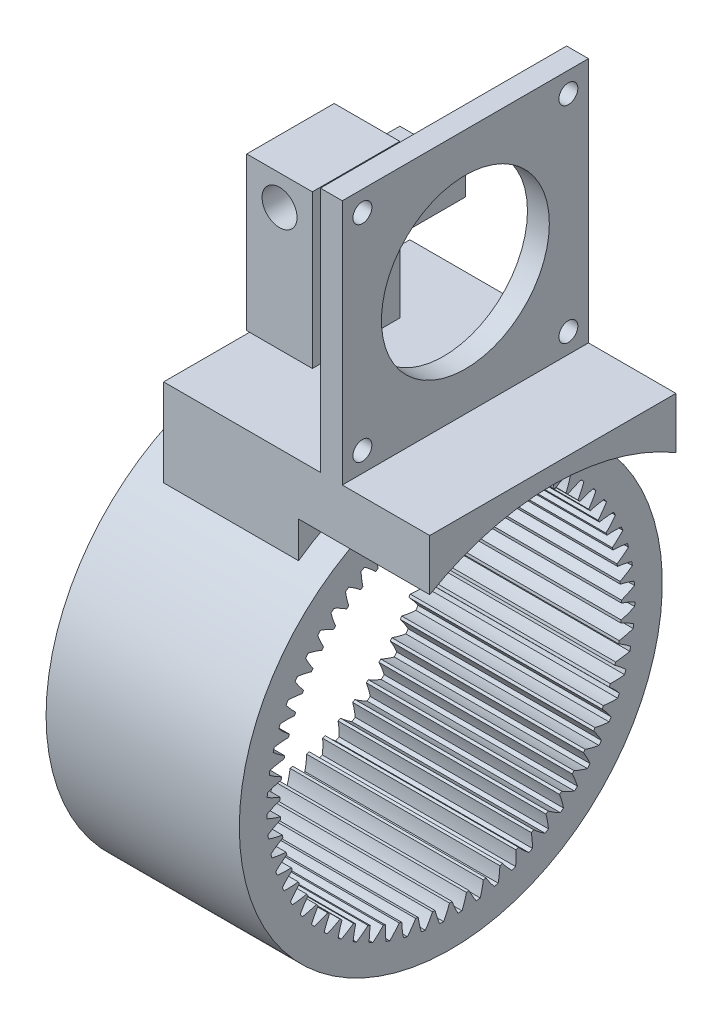
SolidWorks part; units mm, degrees
ref_plane "Plane1" through (0, 0, 0) normal (0, 0, 1) x (1, 0, 0)
ref_plane "Plane2" through (0, 0, 0) normal (0, 1, 0) x (1, 0, 0)
ref_plane "Plane3" through (0, 0, 0) normal (1, 0, 0) x (0, 0, -1)
sketch "HoldingSke" plane through (0, 0, 0) normal (0, 1, 0) x (1, 0, 0)
  line L0 (0, 0) -> (0.5, -0.866)
  line L1 (-15, 0) -> (100, 0) construction
  line L2 (0, 0) -> (-2.1039, 2.3779)
  line L3 (0, 0) -> (-11.863, 4.5341)
  line L4 (0, 0) -> (4.318, 7.479)
  line L5 (0, 0) -> (-23.7986, -8.8762)
  line L6 (0, 0) -> (-10.5278, -7.1032)
  line L7 (-2.1039, 2.3779) -> (3.3635, 27.1825)
  line L8 (-76.2, 3.3779) -> (-54.61, 3.3779)
  line L9 (-71.009, 38.7566) -> (-53.1078, 45.2721)
  line L10 (-76.2, 71.12) -> (104.1128, 71.12)
  line L11 (0, 0) -> (-12, 0)
  line L12 (-76.2, 101.6) -> (-76.162, 101.6)
  line L13 (24.9733, 27.94) -> (52.9518, 28.4284)
  line L14 (24.9733, 27.94) -> (24.9743, 27.94)
  line L15 (24.9733, 27.94) -> (100.4006, 29.5858)
  circle A0 centre (0, 0) radius 12.5
  circle A1 centre (0, 0) radius 12.7
  circle A2 centre (0, 0) radius 12.7
  dimension "MHD" = 25.4
  dimension "Hub_dia" = 25.4
  dimension "Diameter" = 25
  dimension "Num_teeth" = 60
  dimension "Pitch" = 1
  dimension "Overall_len" = 25.4
  dimension "Show_teeth" = 60
  dimension "Thickness" = 12.7
  dimension "OAL" = 25.4001
  dimension "T_dim" = 21.59
  dimension "Ap" = 20
  dimension "H" = 19.05
  dimension "Pitch_radius" = 180.3128
  dimension "Width" = 12
  dimension "Backlash" = 0.038
  dimension "Addendum_fac" = 1
  dimension "Dedendum_fac" = 1.25
  dimension "Clearance_fac" = 0.25
  dimension "Dedendum_add" = 0.001
  dimension "Module" = 1
sketch "BasProSke" plane through (0, 0, 0) normal (0, 1, 0) x (1, 0, 0)
  line L0 (-10, 0) -> (60, 0) construction
  line L1 (0, 29) -> (0, 31.2764)
  line L2 (0, 29) -> (32.815, 29)
  line L3 (32.815, 29) -> (32.815, 31.2764)
  line L4 (32.815, 31.2764) -> (0, 31.2764)
  dimension "Thickness" = 32.815
  dimension "Diameter" = 62.5528
  dimension "Inside_diameter" = 58
revolve "Base-Revolve" add sketch "BasProSke" angle 360 about L0
sketch "TooCutSke" plane through (0, 0, 0) normal (1, 0, 0) x (0, 0, -1)
  line L3 (0.8803, 29.9871) -> (0.8803, 53.6633) construction
  line L4 (0, 0) -> (0, 59.563) construction
  line L5 (0, 0) -> (-3.576, 68.2339) construction
  line L6 (-13.1633, 24.7167) -> (36.4631, 27.3175) construction
  circle A0 centre (0, 0) radius 30 construction
  circle A1 centre (0, 0) radius 31.251 construction
  circle A2 centre (0, 0) radius 25.3717 construction
  circle A3 centre (0, 0) radius 28.9746 construction
  arc A4 (1.2274, 28.9486) -> (0.3395, 31.2492) centre (-13.1633, 24.7167) ccw
  arc A5 (1.2274, 28.9486) -> (-1.2274, 28.9486) centre (0, 0) ccw
  arc A6 (0.3395, 31.2492) -> (-0.3395, 31.2492) centre (0, 0) ccw
  arc A7 (-0.3395, 31.2492) -> (-1.2274, 28.9486) centre (13.1633, 24.7167) ccw
  dimension "Pitch_dia" = 60
  dimension "Base_dia" = 50.7434
  dimension "Root_dia" = 62.502
  dimension "Overcut_dia" = 57.9492
  dimension "Flank_rad" = 15
  dimension "Half_ang" = 3
  dimension "Half_CT" = 0.8803
extrude "ToothCut" cut sketch "TooCutSke" along normal through all
fillet "Breaks" [suppressed] radius 0.1
fillet "RootFillets" [suppressed] radius 0.251
pattern_circular "TeethCuts" count 63 over 360 about axis through (-10, 0, 0) along (1, 0, 0) of "ToothCut"
scale "Scale1" scale about centroid uniform scaling yes scale factor 2
sketch "Sketch1" plane through (49.2225, 0, 0) normal (1, 0, 0) x (0, 0, -1)
  circle A0 centre (0, 0) radius 62.5528
sketch "Sketch2" plane through (49.2225, 0, 0) normal (1, 0, 0) x (0, 0, -1)
  circle A0 centre (0, 0) radius 72.5528
  circle A1 centre (0, 0) radius 62.5528
extrude "Boss-Extrude1" add sketch "Sketch2" against normal blind 65.63
scale "Scale2" scale about centroid uniform scaling yes scale factor 1.1
scale "Scale3" scale about centroid uniform scaling yes scale factor 1.01
scale "Scale4" scale about centroid uniform scaling yes scale factor 0.990099
scale "Scale5" scale about centroid uniform scaling yes scale factor 0.909091
scale "Scale6" scale about centroid uniform scaling yes scale factor 1.01
sketch "Sketch3" plane through (-16.7356, 0, 0) normal (-1, 0, 0) x (0, 0, 1)
  circle A0 centre (0, 0) radius 72.5528
  circle A1 centre (0, 0) radius 73.2783
extrude "Cut-Extrude1" cut sketch "Sketch3" against normal through all
ref_plane "Plane4" through (39.5507, 0, 0) normal (1, 0, 0) x (0, 0, -1)
sketch "Sketch4" plane through (39.5507, 0, 0) normal (1, 0, 0) x (0, 0, -1)
  line L10 (-42.225, 88.9996) -> (-42.225, 58.9996)
  line L11 (42.225, 88.9996) -> (42.225, 58.9996)
  line L12 (0, 0) -> (-42.225, 58.9996) construction
  line L13 (42.225, 58.9996) -> (0, 0) construction
  line L18 (42.225, 88.9996) -> (-42.225, 88.9996)
  arc A0 (42.225, 58.9996) -> (-42.225, 58.9996) centre (0, 0) ccw
  circle A1 centre (0, 0) radius 72.5528 construction
  point P12 (0, 72.5528)
  dimension "D1" = 84.45
  dimension "D3" = 30
extrude "Boss-Extrude2" add sketch "Sketch4" against normal blind 46.2863
scale "Scale7" scale about centroid uniform scaling yes scale factor 0.666667
sketch "Sketch17" plane through (31.8363, 0, 0) normal (1, 0, 0) x (0, 0, -1)
  line L1 (-28.15, 64.6246) -> (-28.15, 44.6246) construction
  line L4 (-28.15, 52.8966) -> (-28.15, 64.6246)
  line L5 (-28.15, 64.6246) -> (28.15, 64.6246)
  line L6 (28.15, 64.6246) -> (28.15, 52.8966)
  arc A1 (28.15, 52.8966) -> (-28.15, 52.8966) centre (0, 5.2915) ccw
  circle A2 centre (0, 5.2915) radius 48.3685 construction
  dimension "D1" = 110.6104
extrude "Boss-Extrude3" add sketch "Sketch17" along normal blind 30
ref_plane "Plane5" through (16.4075, 0, 0) normal (1, 0, 0) x (0, 0, -1)
ref_plane "Plane6" through (41.8363, 0, 0) normal (1, 0, 0) x (0, 0, -1)
sketch "Sketch18" plane through (41.8363, 0, 0) normal (1, 0, 0) x (0, 0, -1)
  line L0 (28.15, 52.8966) -> (28.15, 64.6246) construction
  line L1 (-28.15, 64.6246) -> (28.15, 64.6246)
  line L2 (-28.15, 64.6246) -> (-28.15, 120.9246)
  line L3 (-28.15, 120.9246) -> (28.15, 120.9246)
  line L4 (28.15, 64.6246) -> (28.15, 120.9246)
  line L6 (23.55, 69.1773) -> (-23.55, 69.1773) construction
  line L7 (23.55, 69.1773) -> (23.55, 116.2773) construction
  line L8 (23.55, 116.2773) -> (-23.55, 116.2773) construction
  line L9 (-23.55, 69.1773) -> (-23.55, 116.2773) construction
  line L10 (23.55, 69.1773) -> (-23.55, 116.2773) construction
  line L11 (23.55, 116.2773) -> (-23.55, 69.1773) construction
  circle A1 centre (-23.55, 116.2773) radius 2.165
  circle A2 centre (23.55, 116.2773) radius 2.165
  circle A3 centre (-23.55, 69.1773) radius 2.165
  circle A4 centre (23.55, 69.1773) radius 2.165
  circle A5 centre (0, 92.7273) radius 19.2
  dimension "D2" = 38.4
  dimension "D1" = 56.3
  dimension "D4" = 47.1
  dimension "D5" = 47.1
extrude "Boss-Extrude4" add sketch "Sketch18" against normal blind 5
ref_plane "Plane7" through (0, 0, -1.5) normal (0, 0, 1) x (1, 0, 0)
sketch "Sketch19" plane through (0, 0, -1.5) normal (0, 0, 1) x (1, 0, 0)
  line L0 (36.8363, 64.6246) -> (7.8363, 64.6246) construction
  line L1 (0.9787, 64.6246) -> (36.8363, 64.6246) construction
  line L2 (7.8363, 64.6246) -> (7.8363, 92.7746) construction
  line L4 (0.3363, 99.6246) -> (15.3363, 99.6246)
  line L5 (0.3363, 99.6246) -> (0.3363, 64.6246)
  line L6 (0.3363, 64.6246) -> (15.3363, 64.6246)
  line L7 (15.3363, 99.6246) -> (15.3363, 64.6246)
  line L8 (0.3363, 99.6246) -> (15.3363, 64.6246) construction
  line L9 (0.3363, 64.6246) -> (15.3363, 99.6246) construction
  circle A0 centre (7.8363, 92.7746) radius 4
  point P5 (7.8363, 82.1246)
  dimension "D5" = 8
  dimension "D1" = 29
  dimension "D2" = 28.15
  dimension "D3" = 15
  dimension "D4" = 35
extrude "Boss-Extrude5" add sketch "Sketch19" along normal mid plane 20
sketch "Sketch20" plane through (0.3363, 0, 0) normal (-1, 0, 0) x (0, 0, 1)
  line L0 (-11.5, 99.6246) -> (-11.5, 64.6246) construction
  line L1 (-11.5, 87.6246) -> (-26.5, 87.6246)
  line L2 (-11.5, 87.6246) -> (-11.5, 81.0824)
  line L3 (-11.5, 81.0824) -> (-26.5, 81.0824)
  line L4 (-26.5, 87.6246) -> (-26.5, 81.0824)
  dimension "D1" = 12
  dimension "D2" = 15
extrude "Boss-Extrude6" add sketch "Sketch20" against normal blind 15 separate body
sketch "Sketch21" plane through (0, 87.6246, 0) normal (0, 1, 0) x (1, 0, 0)
  line L0 (15.3363, 26.5) -> (0.3363, 11.5) construction
  line L1 (15.3363, 11.5) -> (15.3363, 26.5) construction
  line L2 (15.3363, 26.5) -> (0.3363, 26.5) construction
  line L3 (15.3363, 11.5) -> (0.3363, 26.5) construction
  circle A0 centre (7.8363, 19) radius 2.165
extrude "Cut-Extrude2" cut sketch "Sketch21" against normal up to next (6.5422 mm away)
sketch "Sketch22" plane through (0, 81.0824, 0) normal (0, -1, 0) x (1, 0, 0)
  line L1 (6.261, -22.7093) -> (10.261, -22.2189)
  line L2 (10.261, -22.2189) -> (11.8363, -18.5095)
  line L3 (11.8363, -18.5095) -> (9.4115, -15.2907)
  line L4 (9.4115, -15.2907) -> (5.4115, -15.7811)
  line L5 (5.4115, -15.7811) -> (3.8363, -19.4905)
  line L6 (3.8363, -19.4905) -> (6.261, -22.7093)
  circle A0 centre (7.8363, -19) radius 3.49 construction
  dimension "D1" = 4
extrude "Cut-Extrude3" cut sketch "Sketch22" against normal blind 3
equation "' \"Module@HoldingSke\" = 6.35"
equation "' \"Num_teeth@HoldingSke\" = 24"
equation "' \"Ap@HoldingSke\" =  14.5"
equation "' \"Ap@HoldingSke\" = 14.5"
equation "' \"Width@HoldingSke\" = 12"
equation "' \"Diameter@HoldingSke\" = 8 * 25.4"
equation "' \"Show_teeth@HoldingSke\" = 100"
equation "' \"Backlash@HoldingSke\" = 0.009 * 25.4"
equation "' \"Addendum_fac@HoldingSke\" = 1.0"
equation "' \"Dedendum_fac@HoldingSke\" = 1.25"
equation "' \"Dedendum_add@HoldingSke\" = 0.00005 * 25.4"
equation "' \"Clearance_fac@HoldingSke\" = 0.25"
equation "\"Pitch@HoldingSke\" = 1 / \"Module@HoldingSke\" "
equation "\"Overcut_dia@TooCutSke\" = (\"Num_teeth@HoldingSke\" - 2 * \"Addendum_fac@HoldingSke\") / \"Pitch@HoldingSke\" - 0.002 * 25.4"
equation "\"Pitch_dia@TooCutSke\" = \"Num_teeth@HoldingSke\" / \"Pitch@HoldingSke\""
equation "\"Base_dia@TooCutSke\" = \"Num_teeth@HoldingSke\" / \"Pitch@HoldingSke\" * cos((\"Ap@HoldingSke\"  * 3.14159265 / 180)) * 0.90"
equation "\"Root_dia@TooCutSke\" = \"Num_teeth@HoldingSke\"  / \"Pitch@HoldingSke\" + 2 *  \"Dedendum_fac@HoldingSke\"/ \"Pitch@HoldingSke\" + \"Dedendum_add@HoldingSke\" * 2"
equation "\"Half_ang@TooCutSke\" = 180 / \"Num_teeth@HoldingSke\""
equation "\"Half_CT@TooCutSke\" = \"Num_teeth@HoldingSke\" / \"Pitch@HoldingSke\" * sin((3.14159265 / 2 / \"Num_teeth@HoldingSke\")) / 2 + 10 * \"Backlash@HoldingSke\" / 4"
equation "\"Flank_rad@TooCutSke\" = \"Num_teeth@HoldingSke\" / \"Pitch@HoldingSke\" / 4"
equation "\"Radius@RootFillets\"= \"Clearance_fac@HoldingSke\" / \"Pitch@HoldingSke\" + \"Dedendum_add@HoldingSke\""
equation "\"Break_rad@Breaks\" = 0.02 / \"Pitch@HoldingSke\" * 5"
equation "\"Diameter@BasProSke\" = \"Num_teeth@HoldingSke\"  / \"Pitch@HoldingSke\" + 2 *  \"Dedendum_fac@HoldingSke\"/ \"Pitch@HoldingSke\" + \"Dedendum_add@HoldingSke\" * 2 + 0.002 * 25.4"
equation "\"Diameter@BasProSke\" = ((sgn( \"Diameter@BasProSke\"  - \"Diameter@HoldingSke\" )+1)*( \"Diameter@BasProSke\"  - \"Diameter@HoldingSke\" ))/2 + \"Diameter@HoldingSke\""
equation "\"Inside_diameter@BasProSke\" =  (\"Num_teeth@HoldingSke\" - 2 * \"Addendum_fac@HoldingSke\") / \"Pitch@HoldingSke\" "
